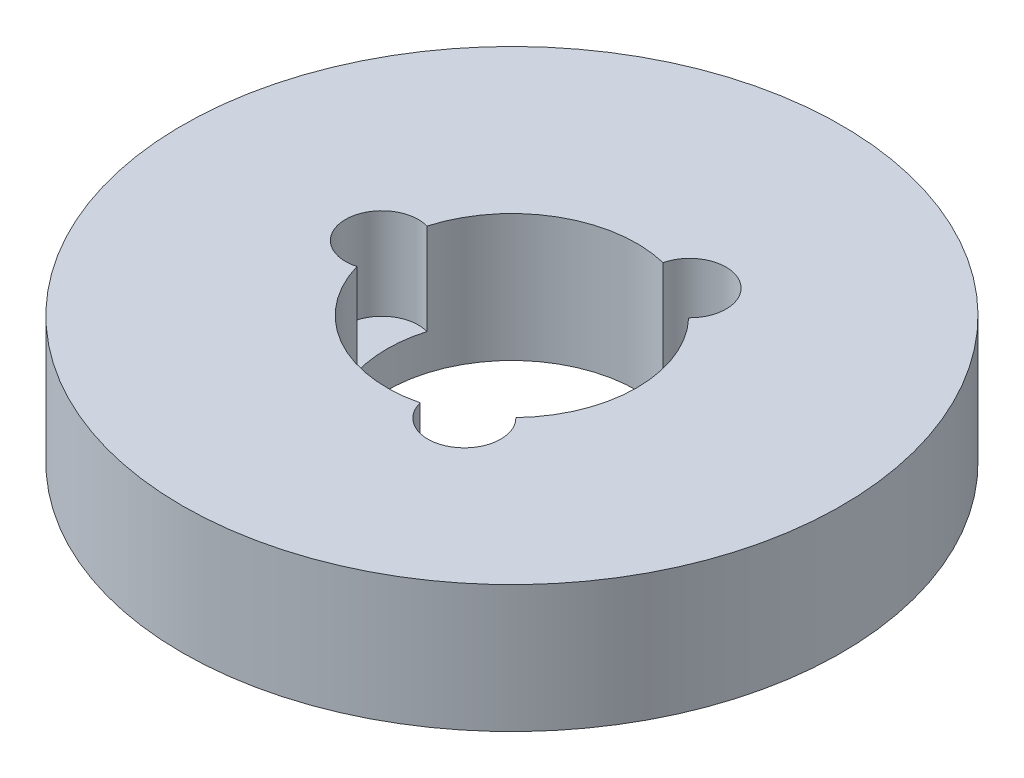
SolidWorks part; units mm, degrees
ref_plane "Front Plane" through (0, 0, 0) normal (0, 0, 1) x (1, 0, 0)
ref_plane "Top Plane" through (0, 0, 0) normal (0, 1, 0) x (1, 0, 0)
ref_plane "Right Plane" through (0, 0, 0) normal (1, 0, 0) x (0, 0, -1)
sketch "Sketch1" plane through (0, 0, 0) normal (0, 1, 0) x (1, 0, 0)
  circle A0 centre (0, 0) radius 72.5
  dimension "FLANGE_OD" = 145
extrude "Boss-Extrude1" add sketch "Sketch1" along normal blind 28
sketch "Sketch2" plane through (0, 0, 0) normal (0, 1, 0) x (1, 0, 0)
  circle A0 centre (0, 0) radius 27.5
  dimension "BORE_D" = 55
extrude "Cut-Extrude1" cut sketch "Sketch2" along normal through all
sketch "Sketch3" plane through (0, 28, 0) normal (0, 1, 0) x (1, 0, 0)
  circle A0 centre (0, 0) radius 28.611 construction
  circle A1 centre (-28.611, 0) radius 8.0153
  dimension "BOLT_D" = 16.0306
  dimension "BOLT_PCD" = 57.2221
extrude "Cut-Extrude2" cut sketch "Sketch3" against normal blind 20.1045
pattern_circular "CirPattern1" count 3 over 360 about axis through (0, 0, 0) along (0, 1, 0) of "Cut-Extrude2"
